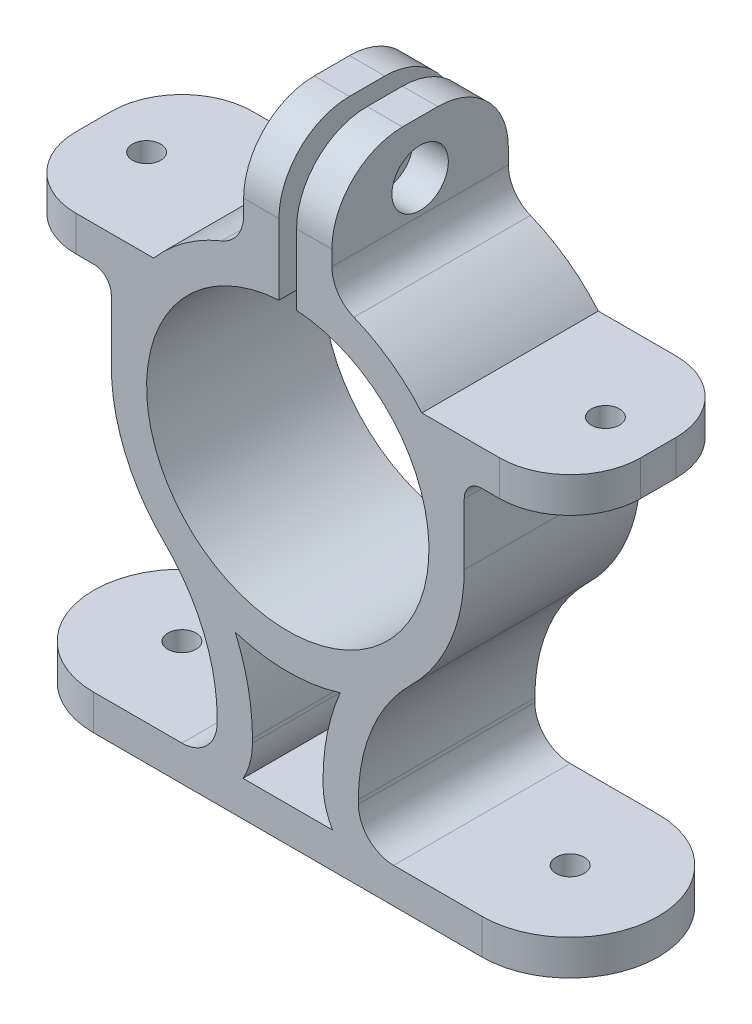
SolidWorks part; units mm, degrees
ref_plane "Front Plane" through (0, 0, 0) normal (0, 0, 1) x (1, 0, 0)
ref_plane "Top Plane" through (0, 0, 0) normal (0, 1, 0) x (1, 0, 0)
ref_plane "Right Plane" through (0, 0, 0) normal (1, 0, 0) x (0, 0, -1)
sketch "Sketch1" plane through (0, 0, 0) normal (0, 0, 1) x (1, 0, 0)
  line L0 (0, 0) -> (65.6061, 0) construction
  line L1 (32.8031, 0) -> (32.8031, 18.5) construction
  line L2 (12.0204, 18.5) -> (55.4995, 18.5) construction
  line L3 (16.803, 0) -> (48.8031, 0)
  line L4 (32.3031, 26.4843) -> (32.3031, 34.4875)
  line L5 (13.0695, 25) -> (55.8846, 25) construction
  line L6 (33.3031, 26.4843) -> (33.3031, 34.4875)
  line L7 (33.3031, 34.4875) -> (35.3032, 34.4875)
  line L8 (35.3032, 34.4875) -> (35.3032, 29.6243)
  line L9 (32.3031, 34.4875) -> (30.3031, 34.4875)
  line L10 (30.3031, 34.4875) -> (30.3031, 29.6243)
  line L11 (22.803, 22) -> (22.803, 18.5)
  line L12 (48.8031, 0) -> (48.8031, 2)
  line L13 (42.8031, 22) -> (42.8031, 18.5)
  line L14 (21.5003, 25) -> (16.803, 25)
  line L15 (16.803, 25) -> (16.803, 23)
  line L16 (16.803, 23) -> (21.803, 23)
  line L17 (44.1058, 25) -> (48.8031, 25)
  line L18 (48.8031, 23) -> (43.8031, 23)
  line L19 (48.8031, 25) -> (48.8031, 23)
  line L20 (16.803, 2) -> (26.803, 2)
  line L21 (16.803, 2) -> (16.803, 0)
  line L22 (28.803, 4) -> (28.803, 4.2171)
  line L23 (48.8031, 2) -> (38.8031, 2)
  line L24 (36.8031, 4) -> (36.8031, 4.2171)
  line L25 (44.1058, 25) -> (40.4025, 25)
  line L26 (21.5003, 25) -> (25.2036, 25)
  line L27 (35.7769, 8.9524) -> (35.7769, 8.9524)
  line L28 (35.7769, 8.9524) -> (35.7769, 8.9524)
  line L29 (35.7769, 8.9524) -> (35.7769, 8.9524)
  line L30 (35.7769, 8.9524) -> (35.7769, 8.9524)
  line L31 (35.7769, 8.9524) -> (35.7769, 8.9524)
  line L32 (35.7769, 8.9524) -> (35.7769, 8.9524)
  line L33 (35.7769, 8.9524) -> (35.7769, 8.9524)
  line L34 (35.7769, 8.9524) -> (35.7769, 8.9524)
  line L35 (34.8031, 4) -> (34.8031, 4.2171)
  line L36 (35.339, 2) -> (35.339, 2)
  line L37 (35.339, 2) -> (35.339, 2)
  line L38 (30.2671, 2) -> (35.339, 2)
  line L39 (30.2671, 2) -> (30.2671, 2)
  line L40 (30.2671, 2) -> (30.2671, 2)
  line L41 (30.803, 4) -> (30.803, 4.2171)
  line L42 (29.8292, 8.9524) -> (29.8292, 8.9524)
  line L43 (29.8292, 8.9524) -> (29.8292, 8.9524)
  line L44 (29.8292, 8.9524) -> (29.8292, 8.9524)
  line L45 (29.8292, 8.9524) -> (29.8292, 8.9524)
  line L46 (29.8292, 8.9524) -> (29.8292, 8.9524)
  line L47 (29.8292, 8.9524) -> (29.8292, 8.9524)
  line L48 (29.8292, 8.9524) -> (29.8292, 8.9524)
  line L49 (29.8292, 8.9524) -> (29.8292, 8.9524)
  arc A0 (32.3031, 26.4843) -> (33.3031, 26.4843) centre (32.8031, 18.5) ccw
  arc A1 (29.8292, 8.9524) -> (35.7769, 8.9524) centre (32.8031, 18.5) ccw
  arc A2 (35.7769, 8.9524) -> (35.7769, 8.9524) centre (35.7769, 8.9524) ccw
  arc A3 (35.7769, 8.9524) -> (35.7769, 8.9524) centre (35.7769, 8.9524) cw
  arc A4 (35.7769, 8.9524) -> (35.7769, 8.9524) centre (35.7769, 8.9524) ccw
  arc A5 (28.803, 4.2171) -> (25.803, 11.3585) centre (18.803, 4.2171) ccw
  arc A6 (36.8031, 4.2171) -> (39.8031, 11.3585) centre (46.8031, 4.2171) cw
  arc A7 (29.053, 27.7703) -> (25.2036, 25) centre (32.8031, 18.5) ccw
  arc A8 (39.8031, 11.3585) -> (42.8031, 18.5) centre (32.8031, 18.5) ccw
  arc A9 (26.803, 2) -> (28.803, 4) centre (26.803, 4) ccw
  arc A10 (38.8031, 2) -> (36.8031, 4) centre (38.8031, 4) cw
  arc A11 (35.3032, 29.6243) -> (36.5532, 27.7702) centre (37.3032, 29.6243) ccw
  arc A12 (30.3031, 29.6243) -> (29.053, 27.7703) centre (28.3031, 29.6243) cw
  arc A13 (43.8031, 23) -> (42.8031, 22) centre (43.8031, 22) ccw
  arc A14 (21.803, 23) -> (22.803, 22) centre (21.803, 22) cw
  arc A15 (40.4025, 25) -> (36.5532, 27.7702) centre (32.8031, 18.5) ccw
  arc A16 (22.803, 18.5) -> (25.803, 11.3585) centre (32.8031, 18.5) ccw
  arc A17 (35.7769, 8.9524) -> (35.7769, 8.9524) centre (35.7769, 8.9524) ccw
  arc A18 (34.8031, 4.2171) -> (35.7769, 8.9524) centre (46.8031, 4.2171) cw
  arc A19 (35.339, 2) -> (34.8031, 4) centre (38.8031, 4) cw
  arc A20 (30.2671, 2) -> (30.803, 4) centre (26.803, 4) ccw
  arc A21 (30.803, 4.2171) -> (29.8292, 8.9524) centre (18.803, 4.2171) ccw
  arc A22 (29.8292, 8.9524) -> (29.8292, 8.9524) centre (29.8292, 8.9524) ccw
  arc A23 (29.8292, 8.9524) -> (29.8292, 8.9524) centre (29.8292, 8.9524) cw
  arc A24 (29.8292, 8.9524) -> (29.8292, 8.9524) centre (29.8292, 8.9524) cw
  arc A25 (29.8292, 8.9524) -> (29.8292, 8.9524) centre (29.8292, 8.9524) cw
  point P39 (36.8031, 9.3348)
  point P42 (40.4025, 25)
  point P45 (25.2036, 25)
  point P48 (28.803, 2)
  dimension "D2" = 2
  dimension "D1" = 10
  dimension "D3" = 1
  dimension "D4" = 2
extrude "Boss-Extrude1" add sketch "Sketch1" along normal blind 10
sketch "Sketch3" plane through (0, 2, 0) normal (0, 1, 0) x (1, 0, 0)
  line L2 (43.8031, -10) -> (48.8031, -10)
  line L3 (48.8031, -10) -> (38.8031, -10) construction
  line L4 (48.8031, -10) -> (48.8031, 0)
  line L5 (48.8031, 0) -> (43.8031, 0)
  arc A0 (43.8031, -10) -> (43.8031, 0) centre (43.8031, -5) ccw
  circle A1 centre (43.8031, -5) radius 0.8
  line M1 (48.8031, 0) -> (38.8031, 0)
  line M3 (38.8031, -10) -> (48.8031, -10)
  line M4 (48.8031, -10) -> (48.8031, 0)
extrude "Cut-Extrude1" cut sketch "Sketch3" against normal blind 2 contours A0 M3 M4 | A0 L4 M1 | A1 region at (47.6863, 2, 8.8832) region at (47.6863, 2, 1.1168) region at (43.8031, 2, 5)
sketch "Sketch4" plane through (0, 2, 0) normal (0, 1, 0) x (1, 0, 0)
  line L0 (21.803, -10) -> (16.803, -10)
  line L1 (16.803, -10) -> (16.803, 0)
  line L2 (16.803, 0) -> (21.803, 0)
  arc A0 (21.803, 0) -> (21.803, -10) centre (21.803, -5) ccw
  circle A1 centre (21.803, -5) radius 0.8
  line M1 (26.803, 0) -> (16.803, 0)
  line M2 (16.803, 0) -> (16.803, -10)
  line M3 (16.803, -10) -> (26.803, -10)
extrude "Cut-Extrude2" cut sketch "Sketch4" against normal blind 2 contours A0 L1 M3 | A0 M1 M2 | A1 region at (17.9198, 2, 1.1168) region at (17.9198, 2, 8.8832) region at (21.803, 2, 5)
sketch "Sketch5" plane through (0, 25, 0) normal (0, 1, 0) x (1, 0, 0)
  line L0 (20.803, -10) -> (16.803, -10)
  line L1 (16.803, -10) -> (16.803, -6)
  line L2 (16.803, -4) -> (16.803, 0)
  line L3 (16.803, 0) -> (20.803, 0)
  line L4 (44.8031, 0) -> (48.8031, 0)
  line L5 (48.8031, 0) -> (48.8031, -4)
  line L6 (48.8031, -6) -> (48.8031, -10)
  line L7 (48.8031, -10) -> (44.8031, -10)
  arc A0 (44.8031, 0) -> (48.8031, -4) centre (44.8031, -4) cw
  arc A1 (48.8031, -6) -> (44.8031, -10) centre (44.8031, -6) cw
  arc A2 (20.803, -10) -> (16.803, -6) centre (20.803, -6) cw
  arc A3 (16.803, -4) -> (20.803, 0) centre (20.803, -4) cw
  circle A4 centre (19.803, -5) radius 0.8
  circle A5 centre (45.8031, -5) radius 0.8
  point P10 (48.8031, 0)
  point P13 (48.8031, -10)
  point P16 (16.803, -10)
  point P19 (16.803, 0)
  dimension "D1" = 4
extrude "Cut-Extrude3" cut sketch "Sketch5" against normal blind 2
ref_axis "Axis1" through (19.803, 19.7556, 5) along (0, 1, 0)
ref_axis "Axis2" through (45.8031, 20.1662, 5) along (0, 1, 0)
ref_axis "Axis3" through (43.8031, -1.9714, 5) along (0, 1, 0)
ref_axis "Axis4" through (21.803, -1.9098, 5) along (0, 1, 0)
ref_axis "Axis5" through (32.8031, 18.5, 14.0547) along (0, 0, -1)
sketch "Sketch6" plane through (30.3031, 0, 0) normal (-1, 0, 0) x (0, 0, 1)
  circle A0 centre (5, 31.4875) radius 0.8
extrude "Cut-Extrude4" cut sketch "Sketch6" against normal blind 3
sketch "Sketch7" plane through (35.3032, 0, 0) normal (1, 0, 0) x (0, 0, -1)
  circle A0 centre (-5, 31.4875) radius 1.6
extrude "Cut-Extrude5" cut sketch "Sketch7" against normal blind 3
ref_axis "Axis6" through (27.0571, 31.4875, 5) along (1, 0, 0)
sketch "Sketch8" plane through (30.3031, 0, 0) normal (-1, 0, 0) x (0, 0, 1)
  line L0 (0, 30.4875) -> (0, 34.4875)
  line L1 (0, 34.4875) -> (4, 34.4875)
  line L2 (6, 34.4875) -> (10, 34.4875)
  line L3 (10, 34.4875) -> (10, 30.4875)
  arc A0 (6, 34.4875) -> (10, 30.4875) centre (6, 30.4875) cw
  arc A1 (0, 30.4875) -> (4, 34.4875) centre (4, 30.4875) cw
  point P10 (10, 34.4875)
  point P13 (0, 34.4875)
  dimension "D1" = 4
extrude "Cut-Extrude6" cut sketch "Sketch8" against normal blind 10
